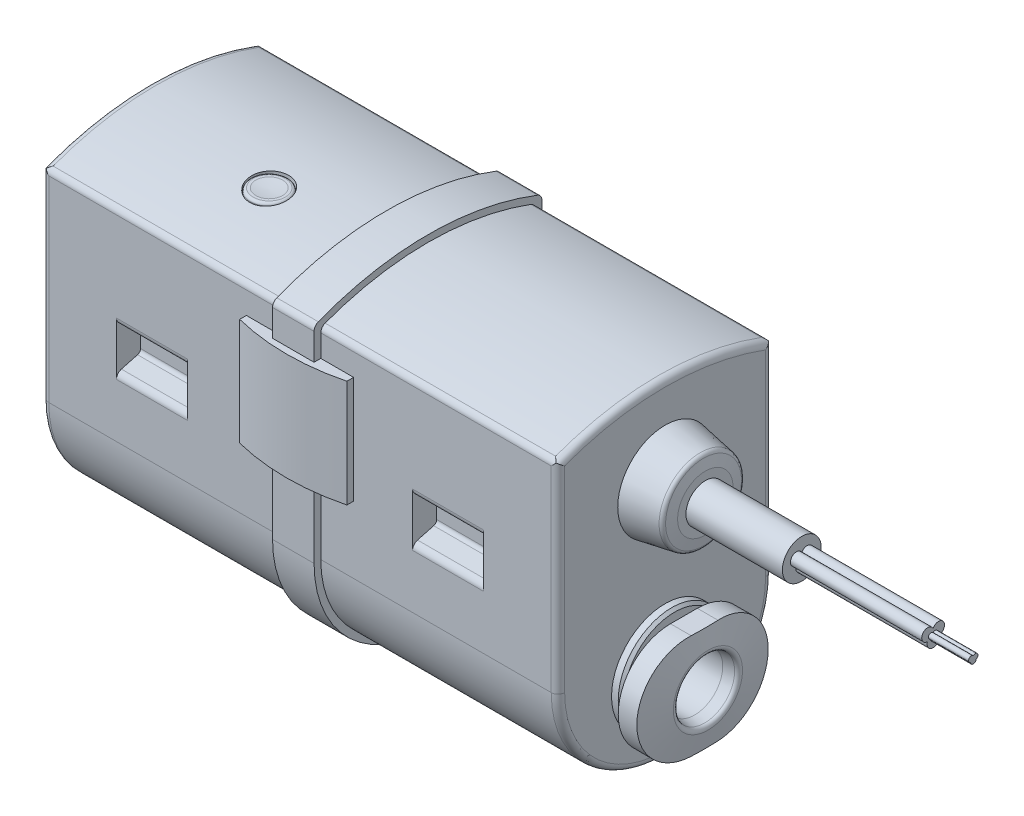
SolidWorks part; units mm, degrees
ref_plane "Front Plane" through (0, 0, 0) normal (0, 0, 1) x (1, 0, 0)
ref_plane "Top Plane" through (0, 0, 0) normal (0, 1, 0) x (1, 0, 0)
ref_plane "Right Plane" through (0, 0, 0) normal (1, 0, 0) x (0, 0, -1)
ref_plane "Plane1" through (0, 0, 0) normal (1, 0, 0) x (0, 0, -1)
sketch "Sketch1" plane through (0, 0, 0) normal (1, 0, 0) x (0, 0, -1)
  line L0 (8, 8) -> (8, 22.6494)
  line L1 (-8, 22.6494) -> (-8, 8)
  arc A0 (-8, 8) -> (8, 8) centre (0, 8) ccw
  arc A1 (8, 22.6494) -> (7.6744, 23.118) centre (7.5, 22.6494) ccw
  arc A2 (7.6744, 23.118) -> (-7.6744, 23.118) centre (0, 2.5) ccw
  arc A3 (-7.6744, 23.118) -> (-8, 22.6494) centre (-7.5, 22.6494) ccw
extrude "Boss-Extrude1" add sketch "Sketch1" against normal blind 19.25 and the other way blind 19.25
ref_plane "Plane2" through (0, 0, 0) normal (0, 1, 0) x (1, 0, 0)
sketch "Sketch2" plane through (0, 0, 0) normal (0, 1, 0) x (1, 0, 0)
  line L0 (0, 18) -> (0, 8)
  line L1 (0, 8) -> (18.75, 8)
  line L2 (19.25, 7.5) -> (19.25, -7.5)
  line L3 (18.75, -8) -> (0, -8)
  line L4 (0, -8) -> (0, -18)
  line L5 (0, -18) -> (29.25, -18)
  line L6 (29.25, -18) -> (29.25, 18)
  line L7 (29.25, 18) -> (0, 18)
  arc A0 (18.75, 8) -> (19.25, 7.5) centre (18.75, 7.5) cw
  arc A1 (19.25, -7.5) -> (18.75, -8) centre (18.75, -7.5) cw
extrude "Cut-Extrude1" cut sketch "Sketch2" along normal blind 25
ref_plane "Plane3" through (0, 0, 0) normal (0, 1, 0) x (1, 0, 0)
sketch "Sketch3" plane through (0, 0, 0) normal (0, 1, 0) x (1, 0, 0)
  line L0 (-29.25, 18) -> (-29.25, -18)
  line L1 (-29.25, -18) -> (0, -18)
  line L2 (0, -18) -> (0, -8)
  line L3 (0, -8) -> (-18.75, -8)
  line L4 (-19.25, -7.5) -> (-19.25, 7.5)
  line L5 (-18.75, 8) -> (0, 8)
  line L6 (0, 8) -> (0, 18)
  line L7 (0, 18) -> (-29.25, 18)
  arc A0 (-18.75, -8) -> (-19.25, -7.5) centre (-18.75, -7.5) cw
  arc A1 (-19.25, 7.5) -> (-18.75, 8) centre (-18.75, 7.5) cw
extrude "Cut-Extrude2" cut sketch "Sketch3" along normal blind 25
ref_plane "Plane4" through (0, 0, 0) normal (0, 0, 1) x (1, 0, 0)
sketch "Sketch4" plane through (0, 0, 0) normal (0, 0, 1) x (1, 0, 0)
  line L0 (-25, 3) -> (-25, -5.0034)
  line L1 (-25, -5.0034) -> (-14, -5.0034)
  line L2 (-14, -5.0034) -> (-14, 0)
  line L3 (-14, 0) -> (-18.75, 0)
  line L4 (-19.25, 0.5) -> (-19.25, 3)
  line L5 (-19.25, 3) -> (-25, 3)
  line L6 (-2, 8) -> (2, 8) construction
  arc A0 (-18.75, 0) -> (-19.25, 0.5) centre (-18.75, 0.5) cw
revolve "Cut-Revolve1" cut sketch "Sketch4" angle 90 about L6 other way angle 90 reverse direction yes
ref_plane "Plane5" through (0, 0, 0) normal (0, 0, 1) x (1, 0, 0)
sketch "Sketch5" plane through (0, 0, 0) normal (0, 0, 1) x (1, 0, 0)
  line L0 (14, -5.0034) -> (25, -5.0034)
  line L1 (25, -5.0034) -> (25, 3)
  line L2 (25, 3) -> (19.25, 3)
  line L3 (19.25, 3) -> (19.25, 0.5)
  line L4 (18.75, 0) -> (14, 0)
  line L5 (14, 0) -> (14, -5.0034)
  line L6 (-2, 8) -> (2, 8) construction
  arc A0 (19.25, 0.5) -> (18.75, 0) centre (18.75, 0.5) cw
revolve "Cut-Revolve2" cut sketch "Sketch5" angle 90 about L6 other way angle 90 reverse direction yes
ref_plane "Plane6" through (0, 0, 0) normal (0, 0, 1) x (1, 0, 0)
sketch "Sketch6" plane through (0, 0, 0) normal (0, 0, 1) x (1, 0, 0)
  line L0 (-24.25, 29.5) -> (-24.25, 22.5)
  line L1 (-24.25, 22.5) -> (-19.25, 22.5)
  line L2 (-19.25, 22.5) -> (-19.25, 24)
  line L3 (-18.75, 24.5) -> (-18.75, 29.5)
  line L4 (-18.75, 29.5) -> (-24.25, 29.5)
  line L5 (-19.25, 2.5) -> (-24.25, 2.5) construction
  arc A0 (-19.25, 24) -> (-18.75, 24.5) centre (-18.75, 24) cw
revolve "Cut-Revolve3" cut sketch "Sketch6" angle 45 about L5 other way angle 45 reverse direction yes
ref_plane "Plane7" through (0, 0, 0) normal (0, 0, 1) x (1, 0, 0)
sketch "Sketch7" plane through (0, 0, 0) normal (0, 0, 1) x (1, 0, 0)
  line L0 (19.25, 24) -> (19.25, 22.5)
  line L1 (19.25, 22.5) -> (24.25, 22.5)
  line L2 (24.25, 22.5) -> (24.25, 29.5)
  line L3 (24.25, 29.5) -> (18.75, 29.5)
  line L4 (18.75, 29.5) -> (18.75, 24.5)
  line L5 (24.25, 2.5) -> (19.25, 2.5) construction
  arc A0 (18.75, 24.5) -> (19.25, 24) centre (18.75, 24) cw
revolve "Cut-Revolve4" cut sketch "Sketch7" angle 45 about L5 other way angle 45 reverse direction yes
ref_plane "Plane8" through (-13.7, 0, 0) normal (1, 0, 0) x (0, 0, -1)
sketch "Sketch8" plane through (-13.7, 0, 0) normal (1, 0, 0) x (0, 0, -1)
  line L0 (-10, 17) -> (-10, 10)
  line L1 (-10, 10) -> (-8, 10)
  line L2 (-8, 10) -> (-8, 12.0163)
  line L3 (-7.6294, 12.4993) -> (-6.4224, 12.8227)
  line L4 (-6.2, 13.1125) -> (-6.2, 14.8875)
  line L5 (-6.4224, 15.1773) -> (-7.6294, 15.5007)
  line L6 (-8, 15.9837) -> (-8, 17)
  line L7 (-8, 17) -> (-10, 17)
  arc A0 (-8, 12.0163) -> (-7.6294, 12.4993) centre (-7.5, 12.0163) cw
  arc A1 (-6.4224, 12.8227) -> (-6.2, 13.1125) centre (-6.5, 13.1125) ccw
  arc A2 (-6.2, 14.8875) -> (-6.4224, 15.1773) centre (-6.5, 14.8875) ccw
  arc A3 (-7.6294, 15.5007) -> (-8, 15.9837) centre (-7.5, 15.9837) cw
extrude "Cut-Extrude3" cut sketch "Sketch8" along normal blind 5.3
ref_plane "Plane9" through (-13.7, 0, 0) normal (1, 0, 0) x (0, 0, -1)
sketch "Sketch9" plane through (-13.7, 0, 0) normal (1, 0, 0) x (0, 0, -1)
  line L0 (6.2, 14.8875) -> (6.2, 13.1125)
  line L1 (6.4224, 12.8227) -> (7.6294, 12.4993)
  line L2 (8, 12.0163) -> (8, 10)
  line L3 (8, 10) -> (10, 10)
  line L4 (10, 10) -> (10, 17)
  line L5 (10, 17) -> (8, 17)
  line L6 (8, 17) -> (8, 15.9837)
  line L7 (7.6294, 15.5007) -> (6.4224, 15.1773)
  arc A0 (6.2, 13.1125) -> (6.4224, 12.8227) centre (6.5, 13.1125) ccw
  arc A1 (7.6294, 12.4993) -> (8, 12.0163) centre (7.5, 12.0163) cw
  arc A2 (8, 15.9837) -> (7.6294, 15.5007) centre (7.5, 15.9837) cw
  arc A3 (6.4224, 15.1773) -> (6.2, 14.8875) centre (6.5, 14.8875) ccw
extrude "Cut-Extrude4" cut sketch "Sketch9" along normal blind 5.3
ref_plane "Plane10" through (13.7, 0, 0) normal (1, 0, 0) x (0, 0, -1)
sketch "Sketch10" plane through (13.7, 0, 0) normal (1, 0, 0) x (0, 0, -1)
  line L0 (-10, 17) -> (-10, 10)
  line L1 (-10, 10) -> (-8, 10)
  line L2 (-8, 10) -> (-8, 12.0163)
  line L3 (-7.6294, 12.4993) -> (-6.4224, 12.8227)
  line L4 (-6.2, 13.1125) -> (-6.2, 14.8875)
  line L5 (-6.4224, 15.1773) -> (-7.6294, 15.5007)
  line L6 (-8, 15.9837) -> (-8, 17)
  line L7 (-8, 17) -> (-10, 17)
  arc A0 (-8, 12.0163) -> (-7.6294, 12.4993) centre (-7.5, 12.0163) cw
  arc A1 (-6.4224, 12.8227) -> (-6.2, 13.1125) centre (-6.5, 13.1125) ccw
  arc A2 (-6.2, 14.8875) -> (-6.4224, 15.1773) centre (-6.5, 14.8875) ccw
  arc A3 (-7.6294, 15.5007) -> (-8, 15.9837) centre (-7.5, 15.9837) cw
extrude "Cut-Extrude5" cut sketch "Sketch10" against normal blind 5.3
ref_plane "Plane11" through (13.7, 0, 0) normal (1, 0, 0) x (0, 0, -1)
sketch "Sketch11" plane through (13.7, 0, 0) normal (1, 0, 0) x (0, 0, -1)
  line L0 (6.2, 14.8875) -> (6.2, 13.1125)
  line L1 (6.4224, 12.8227) -> (7.6294, 12.4993)
  line L2 (8, 12.0163) -> (8, 10)
  line L3 (8, 10) -> (10, 10)
  line L4 (10, 10) -> (10, 17)
  line L5 (10, 17) -> (8, 17)
  line L6 (8, 17) -> (8, 15.9837)
  line L7 (7.6294, 15.5007) -> (6.4224, 15.1773)
  arc A0 (6.2, 13.1125) -> (6.4224, 12.8227) centre (6.5, 13.1125) ccw
  arc A1 (7.6294, 12.4993) -> (8, 12.0163) centre (7.5, 12.0163) cw
  arc A2 (8, 15.9837) -> (7.6294, 15.5007) centre (7.5, 15.9837) cw
  arc A3 (6.4224, 15.1773) -> (6.2, 14.8875) centre (6.5, 14.8875) ccw
extrude "Cut-Extrude6" cut sketch "Sketch11" against normal blind 5.3
ref_plane "Plane12" through (0, 0, 0) normal (1, 0, 0) x (0, 0, -1)
sketch "Sketch12" plane through (0, 0, 0) normal (1, 0, 0) x (0, 0, -1)
  line L0 (8.5, 8) -> (8.5, 22.9939)
  line L1 (-8.5, 22.9939) -> (-8.5, 8)
  arc A0 (-8.5, 8) -> (8.5, 8) centre (0, 8) ccw
  arc A1 (8.5, 22.9939) -> (8.1818, 23.4597) centre (8, 22.9939) ccw
  arc A2 (8.1818, 23.4597) -> (-8.1818, 23.4597) centre (0, 2.5) ccw
  arc A3 (-8.1818, 23.4597) -> (-8.5, 22.9939) centre (-8, 22.9939) ccw
extrude "Boss-Extrude2" add sketch "Sketch12" against normal blind 1.55 and the other way blind 1.55
ref_plane "Plane13" through (0, 0, 0) normal (0, 0, 1) x (1, 0, 0)
sketch "Sketch13" plane through (0, 0, 0) normal (0, 0, 1) x (1, 0, 0)
  line L0 (19.25, 8.1) -> (21.45, 8.1)
  line L1 (21.45, 8.1) -> (22.2028, 8.2347)
  line L2 (22.4455, 8.5817) -> (22.04, 10.9)
  line L3 (22.04, 10.9) -> (20.65, 10.9)
  line L4 (20.65, 10.9) -> (20.65, 8.6)
  line L5 (20.65, 8.6) -> (19.95, 8.6)
  line L6 (19.95, 8.6) -> (19.95, 9.8)
  line L7 (19.95, 9.8) -> (19.75, 10)
  line L8 (19.75, 10) -> (19.25, 10)
  line L9 (19.25, 10) -> (19.25, 8.1)
  line L10 (22.45, 6) -> (19.25, 6) construction
  arc A0 (22.2028, 8.2347) -> (22.4455, 8.5817) centre (22.15, 8.53) ccw
revolve "Revolve1" add sketch "Sketch13" angle 360 about L10 reverse direction yes
ref_plane "Plane14" through (22.45, 0, 0) normal (1, 0, 0) x (0, 0, -1)
sketch "Sketch14" plane through (22.45, 0, 0) normal (1, 0, 0) x (0, 0, -1)
  line L0 (-6, 0) -> (6, 0)
  line L1 (6, 0) -> (6, 12)
  line L2 (6, 12) -> (-6, 12)
  line L3 (-6, 12) -> (-6, 0)
  line L4 (-1, 2.1) -> (1, 2.1)
  line L5 (1, 9.9) -> (-1, 9.9)
  arc A0 (-1, 9.9) -> (-1, 2.1) centre (-1, 6) ccw
  arc A1 (1, 2.1) -> (1, 9.9) centre (1, 6) ccw
extrude "Cut-Extrude7" cut sketch "Sketch14" against normal blind 2
ref_plane "Plane15" through (0, 0, 0) normal (0, 0, 1) x (1, 0, 0)
sketch "Sketch15" plane through (0, 0, 0) normal (0, 0, 1) x (1, 0, 0)
  line L0 (-22.2028, 8.2347) -> (-21.45, 8.1)
  line L1 (-21.45, 8.1) -> (-19.25, 8.1)
  line L2 (-19.25, 8.1) -> (-19.25, 10)
  line L3 (-19.25, 10) -> (-19.75, 10)
  line L4 (-19.75, 10) -> (-19.95, 9.8)
  line L5 (-19.95, 9.8) -> (-19.95, 8.6)
  line L6 (-19.95, 8.6) -> (-20.65, 8.6)
  line L7 (-20.65, 8.6) -> (-20.65, 10.9)
  line L8 (-20.65, 10.9) -> (-22.04, 10.9)
  line L9 (-22.04, 10.9) -> (-22.4455, 8.5817)
  line L10 (-19.25, 6) -> (-22.45, 6) construction
  arc A0 (-22.4455, 8.5817) -> (-22.2028, 8.2347) centre (-22.15, 8.53) ccw
revolve "Revolve2" add sketch "Sketch15" angle 360 about L10 reverse direction yes
ref_plane "Plane16" through (-22.45, 0, 0) normal (1, 0, 0) x (0, 0, -1)
sketch "Sketch16" plane through (-22.45, 0, 0) normal (1, 0, 0) x (0, 0, -1)
  line L0 (-6, 0) -> (6, 0)
  line L1 (6, 0) -> (6, 12)
  line L2 (6, 12) -> (-6, 12)
  line L3 (-6, 12) -> (-6, 0)
  line L4 (-1, 2.1) -> (1, 2.1)
  line L5 (1, 9.9) -> (-1, 9.9)
  arc A0 (-1, 9.9) -> (-1, 2.1) centre (-1, 6) ccw
  arc A1 (1, 2.1) -> (1, 9.9) centre (1, 6) ccw
extrude "Cut-Extrude8" cut sketch "Sketch16" along normal blind 2
ref_plane "Plane17" through (0, 17, 0) normal (0, 1, 0) x (1, 0, 0)
sketch "Sketch17" plane through (0, 17, 0) normal (0, 1, 0) x (1, 0, 0)
  line L0 (-4, -8) -> (-4, -8.5)
  line L1 (4, -8.5) -> (4, -8)
  line L2 (4, -8) -> (-4, -8)
  arc A0 (-4, -8.5) -> (4, -8.5) centre (0, 7.25) ccw
extrude "Boss-Extrude3" add sketch "Sketch17" against normal blind 4 and the other way blind 4
ref_plane "Plane18" through (0, 17, 0) normal (0, 1, 0) x (1, 0, 0)
sketch "Sketch18" plane through (0, 17, 0) normal (0, 1, 0) x (1, 0, 0)
  line L0 (-4, 8) -> (4, 8)
  line L1 (4, 8) -> (4, 8.5)
  line L2 (-4, 8.5) -> (-4, 8)
  arc A0 (4, 8.5) -> (-4, 8.5) centre (0, -7.25) ccw
extrude "Boss-Extrude4" add sketch "Sketch18" against normal blind 4 and the other way blind 4
ref_plane "Plane19" through (0, 0, 2.3) normal (0, 0, 1) x (1, 0, 0)
sketch "Sketch19" plane through (0, 0, 2.3) normal (0, 0, 1) x (1, 0, 0)
  line L0 (-8, 27) -> (-6.55, 27)
  line L1 (-6.55, 27) -> (-6.55, 22)
  line L2 (-6.55, 22) -> (-8, 22)
  line L3 (-8, 22) -> (-8, 27)
  line L4 (-8, 22) -> (-8, 27) construction
revolve "Cut-Revolve5" cut sketch "Sketch19" angle 360 about L4 reverse direction yes
ref_plane "Plane20" through (0, 0, 2.3) normal (0, 0, 1) x (1, 0, 0)
sketch "Sketch20" plane through (0, 0, 2.3) normal (0, 0, 1) x (1, 0, 0)
  line L0 (-7, 24.4) -> (-6.8, 24.4)
  line L1 (-6.6, 24.2) -> (-6.6, 22)
  line L2 (-6.6, 22) -> (-8, 22)
  line L3 (-8, 22) -> (-8, 24.3)
  line L4 (-8, 22) -> (-8, 24.3) construction
  arc A0 (-8, 24.3) -> (-7, 24.4) centre (-8.2945, 32.2946) ccw
  arc A1 (-6.8, 24.4) -> (-6.6, 24.2) centre (-6.8, 24.2) cw
revolve "Revolve3" add sketch "Sketch20" angle 360 about L4 reverse direction yes
ref_plane "Plane21" through (0, 0, 0) normal (0, 0, 1) x (1, 0, 0)
sketch "Sketch21" plane through (0, 0, 0) normal (0, 0, 1) x (1, 0, 0)
  line L0 (19.25, 18) -> (19.25, 21.5378)
  line L1 (19.25, 21.5378) -> (21.8721, 21.0754)
  line L2 (22.1154, 20.8321) -> (22.25, 20.069)
  line L3 (22.25, 20.069) -> (22.25, 19.45)
  line L4 (22.25, 19.45) -> (29.45, 19.45)
  line L5 (29.45, 19.45) -> (29.45, 18)
  line L6 (29.45, 18) -> (19.25, 18)
  line L7 (29.45, 18) -> (19.25, 18) construction
  arc A0 (21.8721, 21.0754) -> (22.1154, 20.8321) centre (21.82, 20.78) cw
revolve "Revolve4" add sketch "Sketch21" angle 360 about L7 reverse direction yes
ref_plane "Plane22" through (39.25, 0, 0) normal (1, 0, 0) x (0, 0, -1)
sketch "Sketch22" plane through (39.25, 0, 0) normal (1, 0, 0) x (0, 0, -1)
  arc A0 (0, 18.4062) -> (-0.424, 17.7506) centre (-0.4, 18.2) ccw
  arc A1 (-0.424, 17.7506) -> (0.424, 17.7506) centre (0, 17.6) ccw
  arc A2 (0.424, 17.7506) -> (0, 18.4062) centre (0.4, 18.2) ccw
extrude "Boss-Extrude5" add sketch "Sketch22" against normal blind 9.8
ref_plane "Plane23" through (39.25, 0, 0) normal (1, 0, 0) x (0, 0, -1)
sketch "Sketch23" plane through (39.25, 0, 0) normal (1, 0, 0) x (0, 0, -1)
  arc A0 (0, 18.1323) -> (-0.1999, 17.8063) centre (-0.15, 18) ccw
  arc A1 (-0.1999, 17.8063) -> (0.1999, 17.8063) centre (0, 17.8) ccw
  arc A2 (0.1999, 17.8063) -> (0, 18.1323) centre (0.15, 18) ccw
extrude "Boss-Extrude6" add sketch "Sketch23" along normal blind 3
